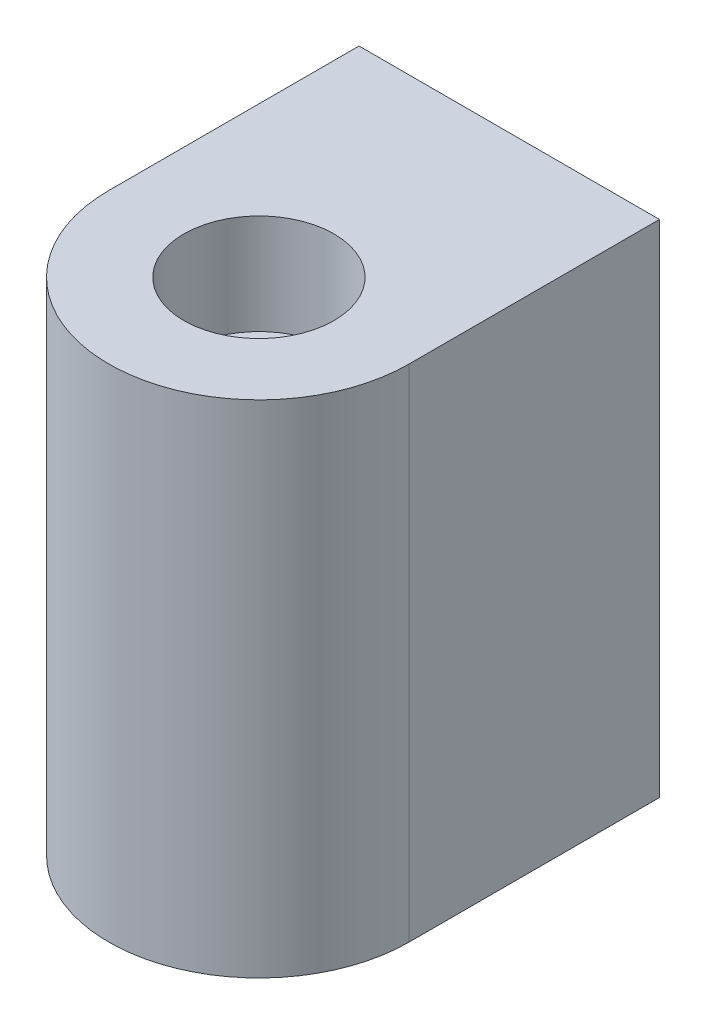
SolidWorks part; units mm, degrees
ref_plane "Ebene vorne" through (0, 0, 0) normal (0, 0, 1) x (1, 0, 0)
ref_plane "Ebene oben" through (0, 0, 0) normal (0, 1, 0) x (1, 0, 0)
ref_plane "Ebene rechts" through (0, 0, 0) normal (1, 0, 0) x (0, 0, -1)
sketch "Sketch1" plane through (0, 0, 0) normal (0, 0, 1) x (1, 0, 0)
  line L1 (-3, 5) -> (3, 5)
  line L2 (-3, 5) -> (-3, -5)
  line L3 (-3, -5) -> (3, -5)
  line L4 (3, 5) -> (3, -5)
  line L5 (-3, 5) -> (3, -5) construction
  line L6 (-3, -5) -> (3, 5) construction
  point P0 (0, 0)
  dimension "D1" = 6
  dimension "D2" = 10
extrude "Boss-Extrude1" add sketch "Sketch1" along normal blind 8
fillet "Fillet2" 2 edges at (3, 0, 8) (-3, 0, 8) type full round first side face at (3, 0, 4) second side face at (-3, 0, 4) middle face at (0, 0, 8)
sketch "Sketch2" plane through (0, 5, 0) normal (0, 1, 0) x (1, 0, 0)
  circle A0 centre (0, -5) radius 1.5
  dimension "D1" = 3
extrude "Cut-Extrude1" cut sketch "Sketch2" against normal blind 2
